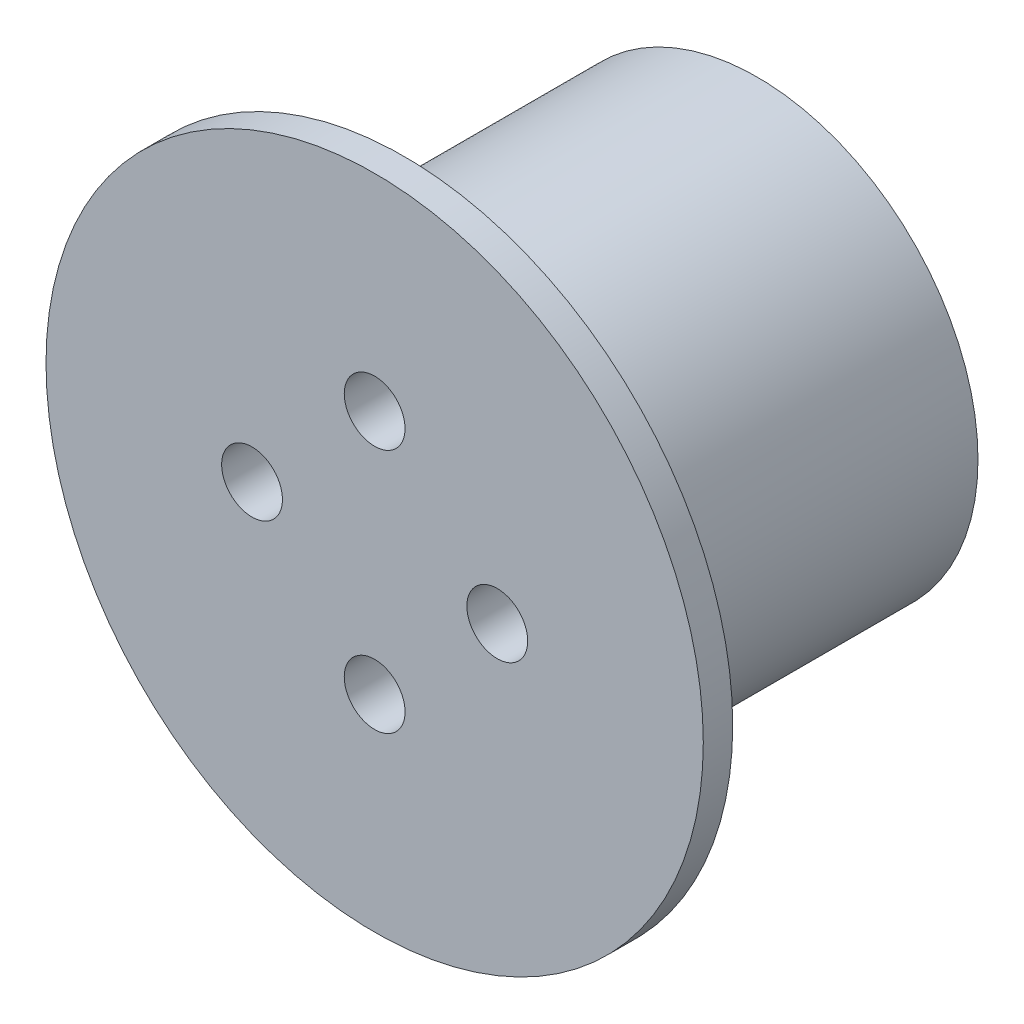
SolidWorks part; units mm, degrees
ref_plane "Front Plane" through (0, 0, 0) normal (0, 0, 1) x (1, 0, 0)
ref_plane "Top Plane" through (0, 0, 0) normal (0, 1, 0) x (1, 0, 0)
ref_plane "Right Plane" through (0, 0, 0) normal (1, 0, 0) x (0, 0, -1)
sketch "Sketch1" plane through (0, 0, 0) normal (0, 0, 1) x (1, 0, 0)
  line L0 (0, 0) -> (0, 3) construction
  circle A0 centre (0, 0) radius 22.5
  circle A1 centre (0, 0) radius 15 construction
  circle A2 centre (0, 15) radius 2.25
  circle A3 centre (15, 0) radius 2.25
  circle A4 centre (0, -15) radius 2.25
  circle A5 centre (-15, 0) radius 2.25
  point P7 (0, 3)
  point P23 (0, 0)
  point P27 (0, 3)
  dimension "D1" = 4
  dimension "D2" = 30
  dimension "D3" = 4.5
extrude "Boss-Extrude1" add sketch "Sketch1" along normal blind 36 contours A2 | A3 | A4 | A5 | A0 A5 A4 A3 A2 region at (0, 0, 0) region at (0, 15, 0) region at (15, 0, 0) region at (0, -15, 0) region at (-15, 0, 0)
extrude "Cut-Extrude1" cut sketch "Sketch1<3>" along normal blind 10 contours A2 | A5 | A4 | A3 region at (0, 15, 0) region at (15, 0, 0) region at (0, -15, 0) region at (-15, 0, 0)
sketch "Sketch1<3>" plane through (0, 0, 0) normal (0, 0, 1) x (1, 0, 0) same geometry as "Sketch1"
sketch "Sketch2" plane through (0, 0, 36) normal (0, 0, 1) x (1, 0, 0)
  circle A0 centre (0, 0) radius 33.5
  circle A1 centre (0, 0) radius 15
  circle M1 centre (0, 0) radius 22.5
  dimension "D1" = 30
  dimension "D2" = 67
extrude "Boss-Extrude2" add sketch "Sketch2" along normal blind 3 contours A0 M1 | A1 M1 | A1 region at (-32.5525, 0, 36) region at (0, 0, 36) region at (-21.8636, 0, 36)
sketch "Sketch3" plane through (0, 0, 36) normal (0, 0, -1) x (-1, 0, 0)
  circle A0 centre (0, 12.5) radius 3.1
  circle A1 centre (12.5, 0) radius 3.1
  circle A2 centre (0, -12.5) radius 3.1
  circle A11 centre (0, 0) radius 18.55 construction
  circle A12 centre (0, 0) radius 12.5 construction
  circle A13 centre (-12.5, 0) radius 3.1
  point P14 (0, 0)
  dimension "D1" = 37.1
  dimension "D2" = 4
extrude "Cut-Extrude2" cut sketch "Sketch3" along normal blind 10 and the other way blind 3
fillet "Fillet1" [suppressed] radius 0.2
